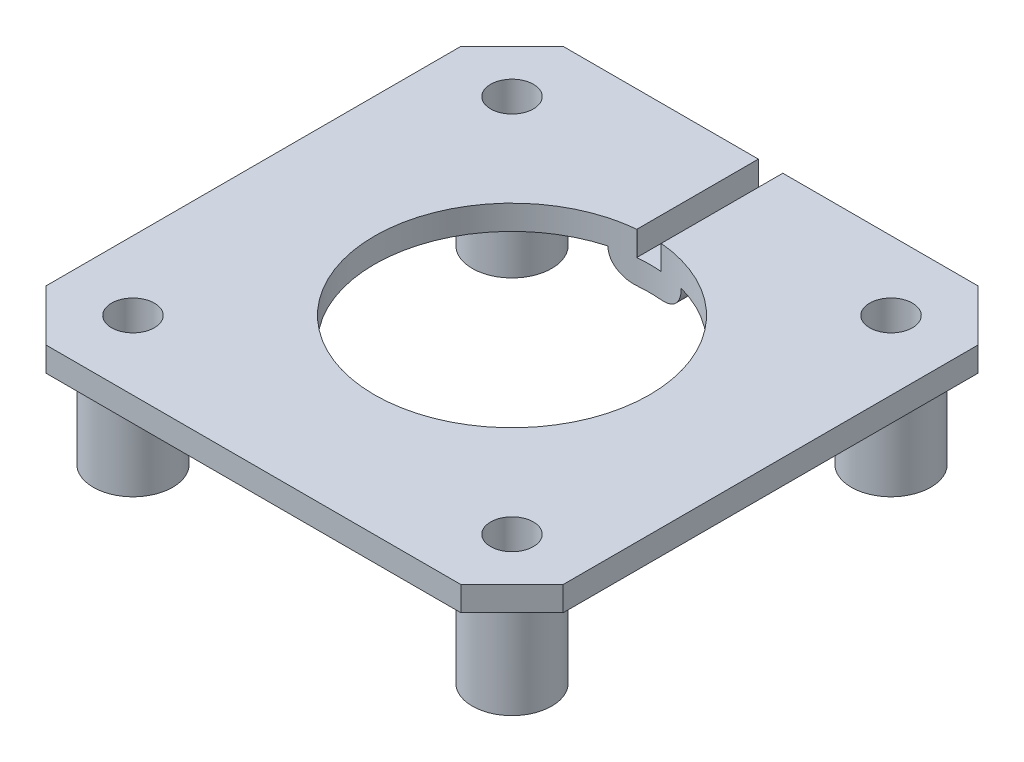
SolidWorks part; units mm, degrees
ref_plane "Front Plane" through (0, 0, 0) normal (0, 0, 1) x (1, 0, 0)
ref_plane "Top Plane" through (0, 0, 0) normal (0, 1, 0) x (1, 0, 0)
ref_plane "Right Plane" through (0, 0, 0) normal (1, 0, 0) x (0, 0, -1)
sketch "Sketch1" plane through (0, 0, 0) normal (0, 1, 0) x (1, 0, 0)
  circle A4 centre (-15.5, 15.5) radius 3.25
  dimension "D3" = 6.5
  dimension "D1" = 15.5
  dimension "D2" = 15.5
extrude "Boss-Extrude1" add sketch "Sketch1" along normal blind 10.55
mirror "Mirror2" about plane through (0, 0, 0) normal (1, 0, 0) of bodies 101
mirror "Mirror3" about plane through (0, 0, 0) normal (0, 0, 1) of bodies 101 102
sketch "Sketch2" plane through (0, 10.55, 0) normal (0, 1, 0) x (1, 0, 0)
  line L1 (-21.15, 21.15) -> (21.15, 21.15)
  line L2 (-21.15, 21.15) -> (-21.15, -21.15)
  line L3 (-21.15, -21.15) -> (21.15, -21.15)
  line L4 (21.15, 21.15) -> (21.15, -21.15)
  line L5 (-21.15, 21.15) -> (21.15, -21.15) construction
  line L6 (-21.15, -21.15) -> (21.15, 21.15) construction
  circle A0 centre (0, 0) radius 11.25
  dimension "D1" = 22.5
  dimension "D4" = 42.3
extrude "Boss-Extrude2" add sketch "Sketch2" against normal blind 2
sketch "Sketch3" plane through (0, 10.55, 0) normal (0, 1, 0) x (1, 0, 0)
  line L0 (-16.9631, 21.15) -> (-21.15, 16.9631)
  line L1 (21.15, 21.15) -> (-21.15, 21.15) construction
  line L2 (-21.15, 21.15) -> (-21.15, -21.15) construction
  line L3 (16.9631, -21.15) -> (21.15, -16.9631)
  line L4 (-21.15, -21.15) -> (21.15, -21.15) construction
  line L5 (21.15, -21.15) -> (21.15, 21.15) construction
  line L6 (-21.15, 16.9631) -> (-21.15, 21.15)
  line L7 (-21.15, 21.15) -> (-16.9631, 21.15)
  line L8 (21.15, -16.9631) -> (21.15, -21.15)
  line L9 (21.15, -21.15) -> (16.9631, -21.15)
  dimension "D1" = 45
  dimension "D2" = 53.9
extrude "Cut-Extrude1" cut sketch "Sketch3" against normal through all
mirror "Mirror4" about plane through (0, 0, 0) normal (0, 0, 1) of "Cut-Extrude1"
sketch "Sketch4" plane through (0, 0, 0) normal (0, -1, 0) x (1, 0, 0)
  circle A1 centre (15.5, -15.5) radius 3.25 construction
  circle A3 centre (15.5, -15.5) radius 1.75
  dimension "D1" = 3.5
extrude "Cut-Extrude2" cut sketch "Sketch4" against normal through all
mirror "Mirror5" about plane through (0, 0, 0) normal (1, 0, 0) of "Cut-Extrude2"
mirror "Mirror6" about plane through (0, 0, 0) normal (0, 0, 1) of "Mirror5"
sketch "Sketch6" plane through (0, 8.55, 0) normal (0, -1, 0) x (1, 0, 0)
  line L0 (0, -21.15) -> (0, -11.25) construction
  line L1 (16.9631, -21.15) -> (-16.9631, -21.15) construction
  line L2 (-3, -21.15) -> (-3, -10.8426)
  line L3 (3, -21.15) -> (3, -10.8426)
  line L4 (3, -21.15) -> (-3, -21.15)
  circle A0 centre (0, 0) radius 11.25 construction
  arc A3 (-3, -10.8426) -> (3, -10.8426) centre (0, 0) ccw
  point P7 (0, -18.325)
  dimension "D1" = 6
  dimension "D2" = 3
extrude "Boss-Extrude3" add sketch "Sketch6" along normal blind 2
sketch "Sketch7" plane through (0, 10.55, 0) normal (0, 1, 0) x (1, 0, 0)
  line L0 (0, 11.25) -> (0, 21.15) construction
  line L1 (16.9631, 21.15) -> (-16.9631, 21.15) construction
  line L2 (-1, 11.25) -> (-1, 21.15)
  line L3 (1, 11.25) -> (1, 21.15)
  circle A0 centre (0, 0) radius 11.25 construction
  arc A1 (-1, 11.25) -> (1, 11.25) centre (0, 11.25) ccw
  arc A2 (1, 21.15) -> (-1, 21.15) centre (0, 21.15) ccw
  point P6 (0, 16.2)
  dimension "D1" = 2
extrude "Cut-Extrude3" cut sketch "Sketch7" against normal blind 2
fillet "Fillet1" radius 2 2 edges at (3, 6.55, -15.9963) (-3, 6.55, -15.9963)
